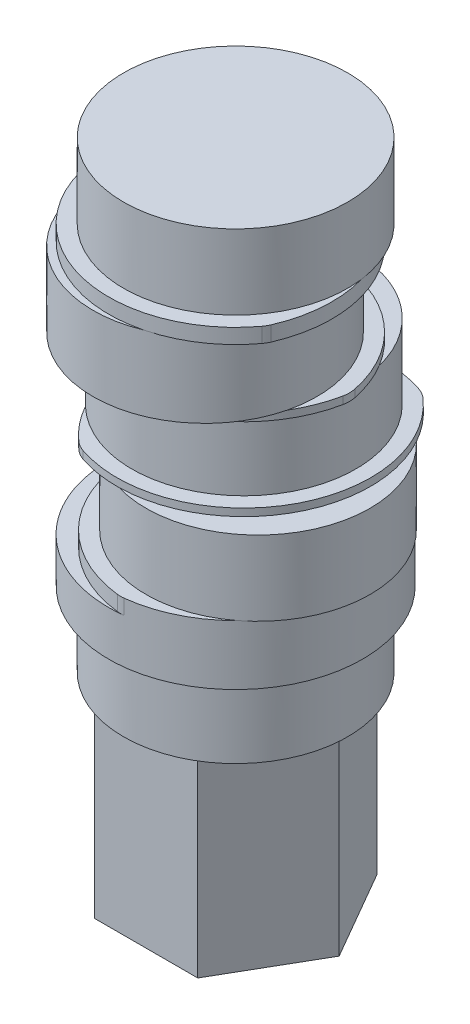
SolidWorks part; units mm, degrees
ref_plane "Front Plane" through (0, 0, 0) normal (0, 0, 1) x (1, 0, 0)
ref_plane "Top Plane" through (0, 0, 0) normal (0, 1, 0) x (1, 0, 0)
ref_plane "Right Plane" through (0, 0, 0) normal (1, 0, 0) x (0, 0, -1)
sketch "Sketch3" plane through (0, 0, 0) normal (0, 1, 0) x (1, 0, 0)
  line L0 (-0.75, 1.299) -> (0, 0) construction
  line L1 (0, 0) -> (-0.75, -1.299) construction
  line L2 (0, 0) -> (1.5, 0) construction
  circle A0 centre (0, 0) radius 1.5 construction
  circle A1 centre (1.5, 0) radius 8.5
  circle A2 centre (-0.75, 1.299) radius 8.5
  circle A3 centre (-0.75, -1.299) radius 8.5
  dimension "D1" = 3
  dimension "D2" = 17
  dimension "D3" = 120
  dimension "D4" = 120
sketch "Sketch4" plane through (0, 0, 0) normal (0, 1, 0) x (1, 0, 0)
  line L1 (-3.4641, 6) -> (-6.9282, 0)
  line L2 (-6.9282, 0) -> (-3.4641, -6)
  line L3 (-3.4641, -6) -> (3.4641, -6)
  line L4 (3.4641, -6) -> (6.9282, 0)
  line L5 (6.9282, 0) -> (3.4641, 6)
  line L6 (3.4641, 6) -> (-3.4641, 6)
  circle A0 centre (0, 0) radius 6 construction
  dimension "D1" = 12
extrude "Boss-Extrude1" add sketch "Sketch4" along normal blind 13
sketch "Sketch5" plane through (0, 13, 0) normal (0, 1, 0) x (1, 0, 0)
  circle A0 centre (0, 0) radius 7.5
  dimension "D1" = 15
extrude "Boss-Extrude2" add sketch "Sketch5" along normal blind 8
sketch "Sketch6" plane through (0, 21, 0) normal (0, 1, 0) x (1, 0, 0)
  circle A0 centre (0, 0) radius 8.5
  circle A1 centre (1.5, 0) radius 8.5
  circle M1 centre (0, 0) radius 7.5
  dimension "D1" = 17
extrude "Boss-Extrude3" add sketch "Sketch6" along normal blind 1 contours A1 M1 | A0 A1 M1 region at (6.1121, 21, 5.5946) region at (0.1719, 21, 0)
sketch "Sketch7" plane through (0, 22, 0) normal (0, 1, 0) x (1, 0, 0)
  circle A0 centre (1.5, 0) radius 7.5
  arc A1 (-4.5833, 5.9366) -> (-4.5833, -5.9366) centre (0, 0) ccw construction
extrude "Boss-Extrude4" add sketch "Sketch7" along normal blind 5
sketch "Sketch8" plane through (0, 27, 0) normal (0, 1, 0) x (1, 0, 0)
  circle A0 centre (1.5, 0) radius 8.5
  circle A1 centre (-0.75, 1.299) radius 8.5
  circle A2 centre (1.5, 0) radius 8.5 construction
  circle M1 centre (1.5, 0) radius 7.5
extrude "Boss-Extrude5" add sketch "Sketch8" along normal blind 0.5 contours A1 M1 | A1 A0 M1 region at (5.5922, 27, -6.6403) region at (0.8921, 27, -0.3509)
sketch "Sketch9" plane through (0, 27.5, 0) normal (0, 1, 0) x (1, 0, 0)
  circle A0 centre (-0.75, 1.299) radius 7.5
  arc A1 (-0.6012, -7.1997) -> (6.6845, 5.4195) centre (1.5, 0) ccw construction
extrude "Boss-Extrude6" add sketch "Sketch9" along normal blind 5
sketch "Sketch11" plane through (0, 32.5, 0) normal (0, 1, 0) x (1, 0, 0)
  circle A0 centre (-0.75, 1.299) radius 8.5
  circle A1 centre (-0.75, -1.299) radius 8.5
  arc A2 (-3.8251, -6.6252) -> (4.5751, 7.9243) centre (-0.75, 1.299) ccw construction
  circle M1 centre (-0.75, 1.299) radius 7.5
extrude "Boss-Extrude7" add sketch "Sketch11" along normal blind 0.5 contours A1 M1 | A0 A1 M1 region at (-8.5574, 32.5, -1.5267) region at (-0.75, 32.5, -0.5972)
sketch "Sketch12" plane through (0, 33, 0) normal (0, 1, 0) x (1, 0, 0)
  circle A0 centre (-0.75, -1.299) radius 7.5
  arc A1 (6.5357, 3.0792) -> (-8.0357, 3.0792) centre (-0.75, 1.299) ccw construction
extrude "Boss-Extrude8" add sketch "Sketch12" along normal blind 5
sketch "Sketch13" plane through (0, 38, 0) normal (0, 1, 0) x (1, 0, 0)
  circle A0 centre (-0.75, -1.299) radius 8.5
  circle A1 centre (0, 0) radius 8.5
  arc A3 (7.6501, 0) -> (-9.1501, 0) centre (-0.75, -1.299) ccw construction
  circle M1 centre (-0.75, -1.299) radius 7.5
extrude "Boss-Extrude9" add sketch "Sketch13" along normal blind 1 contours A1 M1 | A1 A0 M1 region at (7.3307, 38, 3.0859) region at (-0.664, 38, 1.1501)
sketch "Sketch14" plane through (0, 39, 0) normal (0, 1, 0) x (1, 0, 0)
  circle A0 centre (0, 0) radius 7.5
  arc A1 (6.5357, 3.0792) -> (-8.0357, 3.0792) centre (-0.75, 1.299) ccw construction
extrude "Boss-Extrude10" add sketch "Sketch14" along normal blind 5
fillet "Fillet1" radius 2 8 edges at (0.75, 21.5, -8.4668) (0.75, 21.5, 8.4668) (-3.8251, 27.25, 6.6252) (4.5751, 27.25, -7.9243) (7.6501, 32.75, 0) (-9.1501, 32.75, 0) (-7.7075, 38.5, -3.5839) (6.9575, 38.5, 4.8829)
sketch "Sketch15" plane through (0, 21, 0) normal (0, -1, 0) x (1, 0, 0)
  circle A0 centre (0, 0) radius 8.5
  dimension "D1" = 17
extrude "Boss-Extrude11" add sketch "Sketch15" along normal blind 3
equation "\"N_pin\"= 24"
equation "\"R_pin\"= 60"
equation "\"d_pin\"= 13"
equation "\"e\"= 1.5"
equation "\"t_disk\"= 5"
equation "\"N_outpin\"= 8"
equation "\"R_outpin\"= 34"
equation "\"d_outpin\"= 13"
equation "\"N_lobes\"= \"N_pin\" - 1"
equation "\"d_outhole\"= \"d_outpin\" + 2 * \"e\""
equation "\"ratio\"= \"N_lobes\""
equation "\"d_center\"= 24"
equation "\"a_hole1\"= 0 / \"N_lobes\""
equation "\"a_hole2\"= 360 / \"N_disk\" / \"N_lobes\""
equation "\"a_hole3\"= 720 / \"N_disk\" / \"N_lobes\""
equation "\"N_disk\"= 3"
equation "\"t_gap\"= 0.5"
equation "\"L_stack\"= \"N_disk\" * \"t_disk\" + (\"N_disk\" - 1) * \"t_gap\""
equation "\"d_pinshaft\"= 6"
equation "\"d_ecc\"= 15"
equation "\"d_outbrg\"= 47"
equation "\"w_outbrg\"= 7"
equation "\"d_outshaft\"= 35"
equation "\"w_brg\"= 5"
equation "\"D1@Boss-Extrude5\"=\"t_gap\""
equation "\"D1@Boss-Extrude7\"=\"t_gap\""
equation "\"c_run\"= 0.5"
equation "\"c_ax\"= 0.3"
equation "\"D_pocket\"= 2 * \"R_pin\" + \"d_pin\" + 2 * \"c_run\""
equation "\"h_pocket\"= \"L_stack\" + 2 * \"c_ax\""
equation "\"t_floor\"= 8"
equation "\"d_insert\"= 5.6"
equation "\"N_bolt\"= 8"
equation "\"R_bolt\"= \"D_pocket\" / 2 + 2 + \"d_insert\" / 2"
equation "\"D_housing\"= 2 * (\"R_bolt\" + \"d_insert\" / 2 + 2.5)"
equation "\"D1@Boss-Extrude2\"=\"t_floor\""
equation "\"D1@Sketch5\"=\"d_ecc\""
equation "\"D1@Boss-Extrude10\"=\"w_brg\""
equation "\"D1@Boss-Extrude8\"=\"w_brg\""
equation "\"D1@Boss-Extrude6\"=\"w_brg\""
equation "\"D1@Boss-Extrude4\"=\"w_brg\""
equation "\"D1@Sketch6\"=\"d_ecc\"+2"
equation "\"D1@Sketch15\"=\"d_ecc\"+2"
equation "\"D1@Boss-Extrude11\"=\"t_floor\"-\"w_brg\""
